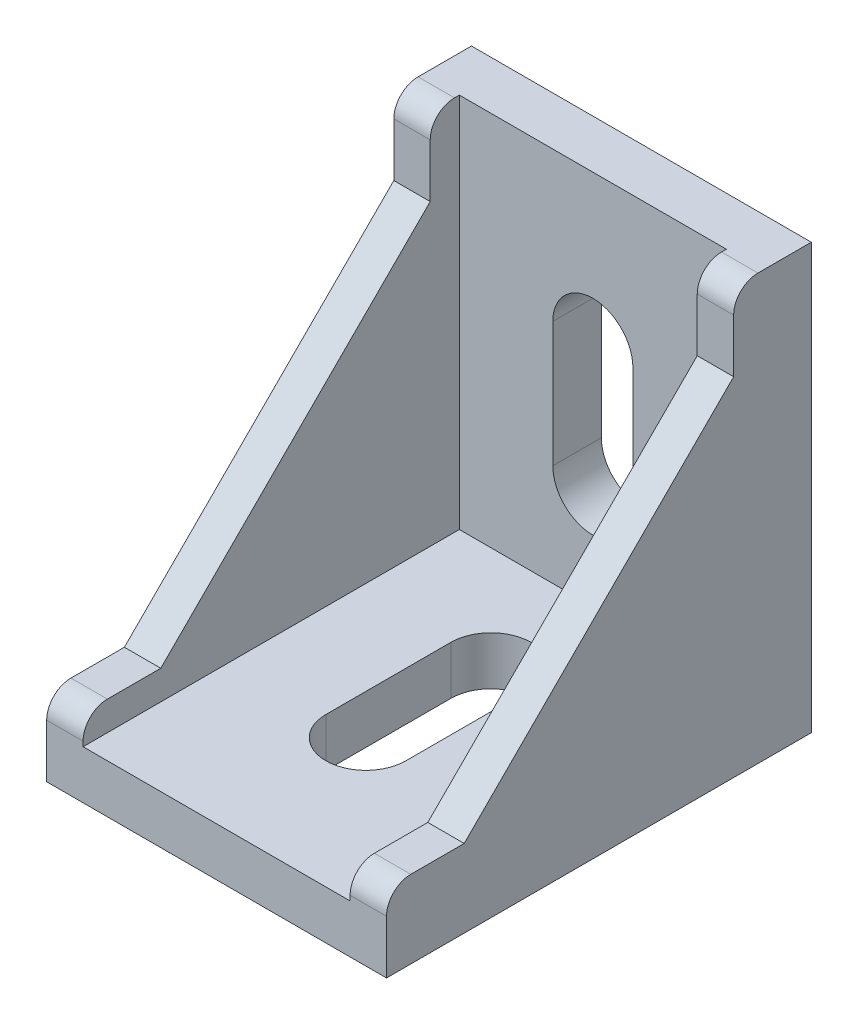
SolidWorks part; units mm, degrees
note: '?' marks a value the reader was unsure of.
ref_plane "Front Plane" through (0, 0, 0) normal (0, 0, 1) x (1, 0, 0)
ref_plane "Top Plane" through (0, 0, 0) normal (0, 1, 0) x (1, 0, 0)
ref_plane "Right Plane" through (0, 0, 0) normal (1, 0, 0) x (0, 0, -1)
ref_axis "Axis_X" through (-15.4, 0, 0) along (1, 0, 0)?
ref_axis "Axis_Y" through (0, 36.855, 0) along (0, -1, 0)?
ref_axis "Axis_Z" through (0, 0, -3.955) along (0, 0, 1)?
sketch "Sketch1" plane through (0, 0, 0) normal (1, 0, 0) x (0, 0, -1)
  line L1 (0, 0) -> (-35, 0)
  line L2 (0, 0) -> (0, 35)
  line L3 (0, 35) -> (-35, 35)
  line L4 (-35, 0) -> (-35, 35)
  dimension "H" = 35
extrude "Boss-Extrude1" add sketch "Sketch1" along normal mid plane 28
sketch "Sketch2" plane through (-14, 0, 0) normal (-1, 0, 0) x (0, 0, 1)
  line L0 (35, 35) -> (6.4, 35)
  line L1 (0, 35) -> (35, 35) construction
  line L2 (6.4, 35) -> (35, 6.4)
  line L3 (35, 35) -> (35, 0) construction
  line L4 (35, 6.4) -> (35, 35)
  line L5 (0, 0) -> (0, 35) construction
  dimension "W1" = 6.4
extrude "Cut-Extrude1" cut sketch "Sketch2" against normal through all
sketch "Sketch3" plane through (0, 35, 0) normal (0, 1, 0) x (1, 0, 0)
  line L0 (14, -35) -> (-14, -35) construction
  line L1 (-11, -35) -> (11, -35)
  line L2 (-11, -35) -> (-11, -4)
  line L3 (-11, -4) -> (11, -4)
  line L4 (11, -35) -> (11, -4)
  line L5 (0, 0) -> (0, -4) construction
  line L6 (14, 0) -> (-14, 0) construction
  line L7 (-14, 0) -> (-14, -6.4) construction
  dimension "T" = 4
  dimension "T1" = 3
extrude "Cut-Extrude2" cut sketch "Sketch3" against normal offset from surface (31 mm away) 4 up to face at (0, 0, 17.5)
sketch "Sketch4" plane through (-14, 0, 0) normal (-1, 0, 0) x (0, 0, 1)
  line L0 (6.4, 35) -> (6.4, 28.6)
  line L1 (6.4, 28.6) -> (28.6, 6.4)
  line L2 (28.6, 6.4) -> (35, 6.4)
  line L3 (0, 0) -> (0, 35) construction
  line L4 (0, 35) -> (6.4, 35) construction
  line L5 (35, 6.4) -> (35, 0) construction
  line L6 (6.4, 35) -> (35, 6.4)
  dimension "W1" = 6.4
  dimension "FIX_1" = 6.4
extrude "Cut-Extrude3" cut sketch "Sketch4" against normal through all
fillet "Fillet1" radius 2 4 edges at (12.5, 6.4, 35) (-12.5, 6.4, 35) (12.5, 35, 6.4) (-12.5, 35, 6.4)
sketch "Sketch5" plane through (0, 0, 4) normal (0, 0, 1) x (1, 0, 0)
  line L0 (0, 12.4) -> (0, 22.7) construction
  line L1 (-3.3, 12.4) -> (-3.3, 22.7)
  line L2 (3.3, 12.4) -> (3.3, 22.7)
  line L3 (14, 0) -> (-14, 0) construction
  arc A0 (-3.3, 12.4) -> (3.3, 12.4) centre (0, 12.4) ccw
  arc A1 (3.3, 22.7) -> (-3.3, 22.7) centre (0, 22.7) ccw
  point P2 (0, 17.55)
  dimension "R" = 3.3
  dimension "B" = 10.3
  dimension "A" = 12.4
extrude "Cut-Extrude4" cut sketch "Sketch5" against normal through all
sketch "Sketch6" plane through (0, 4, 0) normal (0, 1, 0) x (1, 0, 0)
  line L0 (0, -12.4) -> (0, -22.7) construction
  line L1 (3.3, -12.4) -> (3.3, -22.7)
  line L2 (-3.3, -12.4) -> (-3.3, -22.7)
  line L3 (14, 0) -> (-14, 0) construction
  arc A0 (3.3, -12.4) -> (-3.3, -12.4) centre (0, -12.4) ccw
  arc A1 (-3.3, -22.7) -> (3.3, -22.7) centre (0, -22.7) ccw
  point P2 (0, -17.55)
  dimension "R" = 3.3
  dimension "B" = 10.3
  dimension "A" = 12.4
extrude "Cut-Extrude5" cut sketch "Sketch6" against normal through all
sketch "Sketch7" plane through (0, 0, 0) normal (0, 0, -1) x (-1, 0, 0)
  line L0 (0, 35) -> (0, 0) construction
  line L1 (-2.9, 32.3) -> (2.9, 32.3)
  line L2 (-2.9, 32.3) -> (-2.9, 29.7)
  line L3 (-2.9, 29.7) -> (2.9, 29.7)
  line L4 (2.9, 32.3) -> (2.9, 29.7)
  line L5 (-2.9, 5.3) -> (2.9, 5.3)
  line L6 (-2.9, 5.3) -> (-2.9, 2.7)
  line L7 (-2.9, 2.7) -> (2.9, 2.7)
  line L8 (2.9, 5.3) -> (2.9, 2.7)
  line L9 (-14, 35) -> (14, 35) construction
  line L10 (-14, 0) -> (14, 0) construction
  dimension "W" = 5.8
  dimension "MSM_1" = 2.6
extrude "Boss-Extrude2" add sketch "Sketch7" along normal blind 2.1
sketch "Sketch8" plane through (0, 0, 0) normal (0, -1, 0) x (1, 0, 0)
  line L0 (0, 0) -> (0, 35) construction
  line L1 (-2.9, 32.3) -> (2.9, 32.3)
  line L2 (-2.9, 32.3) -> (-2.9, 29.7)
  line L3 (-2.9, 29.7) -> (2.9, 29.7)
  line L4 (2.9, 32.3) -> (2.9, 29.7)
  line L5 (-2.9, 5.3) -> (2.9, 5.3)
  line L6 (-2.9, 5.3) -> (-2.9, 2.7)
  line L7 (-2.9, 2.7) -> (2.9, 2.7)
  line L8 (2.9, 5.3) -> (2.9, 2.7)
  line L9 (14, 35) -> (-14, 35) construction
  line L10 (14, 0) -> (-14, 0) construction
  dimension "W" = 5.8
  dimension "MSM_1" = 2.6
extrude "Boss-Extrude3" add sketch "Sketch8" along normal blind 2.1
hole_wizard "Tap1" [suppressed] positions "Sketch11" profile "Sketch10" hole size "M5x0.8" standard "JIS"
sketch "Sketch11" plane through (-9.8, 0, 0) normal (-1, 0, 0) x (0, 0, 1)
  line L0 (27.6, 0) -> (0, 0) construction
  line L1 (0, 0) -> (0, 27.6) construction
  point P0 (8, 8)
  dimension "KSS_1" = 12
  dimension "KSS_2" = 12
sketch "Sketch10" plane through (-9.8, 8, 8) normal (0, 1, 0) x (0, 0, 1)
  line L0 (0, 0) -> (0, 19.6)
  line L1 (0, 19.6) -> (2.067, 19.6)
  line L2 (2.067, 19.6) -> (2.067, 0)
  line L5 (2.067, 0) -> (0, 0)
  line L11 (0, -6.35) -> (0, 107.95) construction
  dimension "FIX_5" = 4.134
  dimension "Thru Hole Depth" = 19.6
cosmetic thread "Thread1" [suppressed] parameters "FIX_4"=5
equation "\"Factor\"= 1.082532"
equation "\"KSS_1@Sketch11\" = if ( \"L@Boss-Extrude1\" < 20 , 8 , 12 )"
equation "\"KSS_2@Sketch11\"= if ( \"L@Boss-Extrude1\" < 20 , 8 , 12 )"
